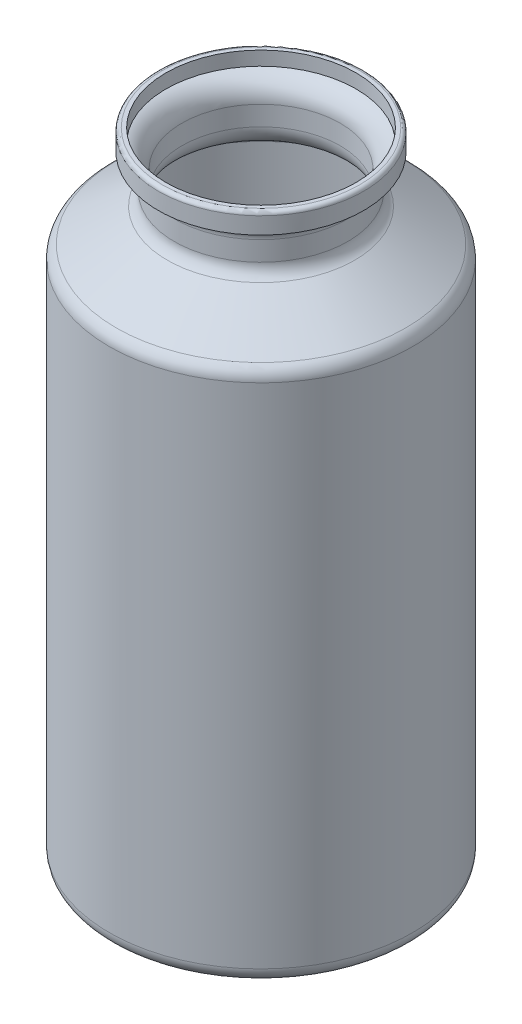
SolidWorks part; units mm, degrees
ref_plane "Front Plane" through (0, 0, 0) normal (0, 0, 1) x (1, 0, 0)
ref_plane "Top Plane" through (0, 0, 0) normal (0, 1, 0) x (1, 0, 0)
ref_plane "Right Plane" through (0, 0, 0) normal (1, 0, 0) x (0, 0, -1)
sketch "Sketch5" plane through (0, 0, 0) normal (0, 0, 1) x (1, 0, 0)
  line L0 (0, 135.4839) -> (0, -149.0323) construction
  line L1 (-127.3548, 0) -> (186.1935, 0) construction
  line L4 (0, -74.1935) -> (40, -74.1935)
  line L5 (40, 65.8065) -> (40, -74.1935)
  line L6 (40, 65.8065) -> (22.8818, 76.8933)
  line L10 (22.8818, 88.2282) -> (22.8818, 76.8933)
  line L11 (0, -74.1935) -> (0, 93.634)
  line L12 (0, 93.634) -> (27.067, 93.634)
  line L14 (22.8818, 88.2282) -> (27.067, 88.2282)
  line L15 (27.067, 93.634) -> (27.067, 88.2282)
  dimension "D1" = 40
  dimension "D2" = 140
revolve "Revolve1" add sketch "Sketch5" angle 360 about L11
fillet "Fillet1" radius 4 4 edges at (0, 88.2282, -22.8818) (0, 76.8933, -22.8818) (0, 65.8065, -40) (0, -74.1935, -40)
fillet "Fillet2" radius 1 1 edges at (0, 93.634, -27.067)
shell "Shell1" thickness 2 removed face at (0, 93.634, 26.067)
